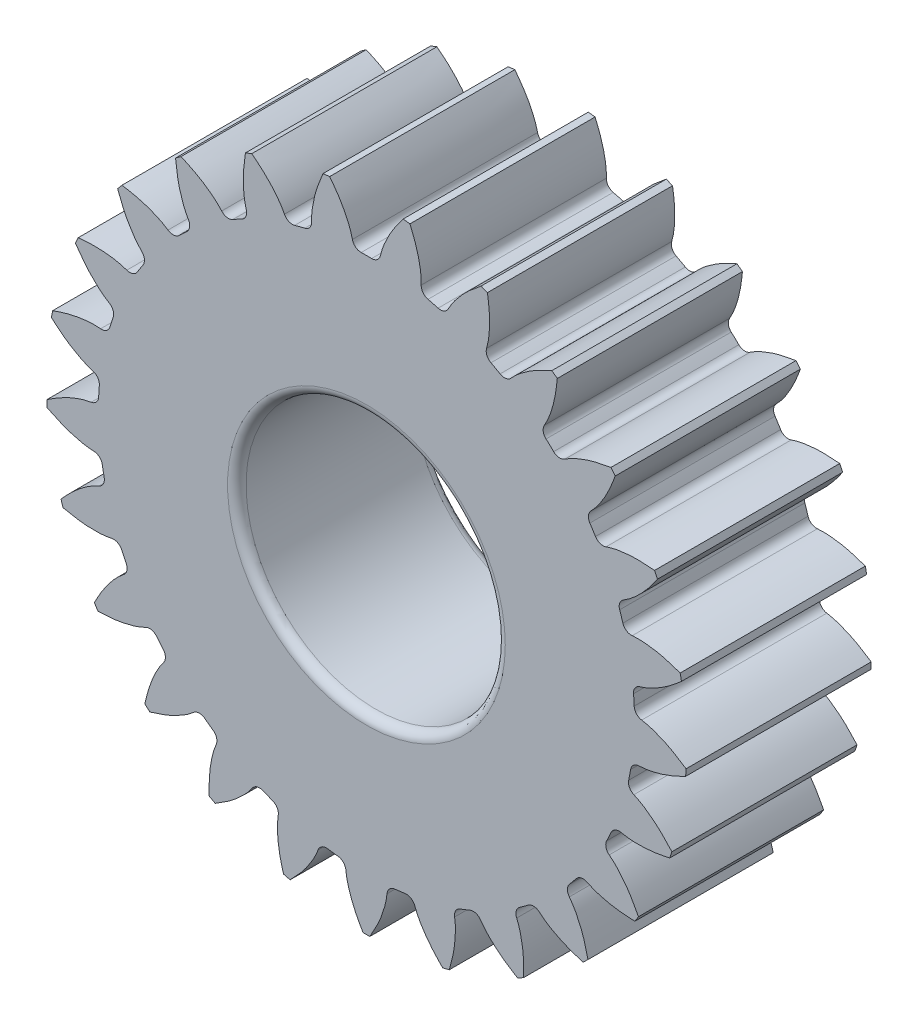
SolidWorks part; units mm, degrees
ref_plane "前视基准面" through (0, 0, 0) normal (0, 0, 1) x (1, 0, 0)
ref_plane "上视基准面" through (0, 0, 0) normal (0, 1, 0) x (1, 0, 0)
ref_plane "右视基准面" through (0, 0, 0) normal (1, 0, 0) x (0, 0, -1)
ref_axis "基准轴1" through (0, 0, -88.99) along (0, 0, 1)
sketch "草图1" plane through (0, 0, 0) normal (0, 0, 1) x (1, 0, 0)
  circle A0 centre (0, 0) radius 34.575
extrude "凸台-拉伸1" add sketch "草图1" along normal blind 20
sketch "草图2" plane through (0, 0, 0) normal (0, 0, -1) x (-1, 0, 0)
  arc A0 (0.5647, 28.9445) -> (-0.5647, 28.9445) centre (0, 0) ccw
  circle A1 centre (0, 0) radius 34.575
  arc A2 (3.9686, 34.3465) -> (-3.9686, 34.3465) centre (0, 0) ccw
  arc A3 (0.5647, 28.9445) -> (1.5123, 29.6963) centre (0.5832, 29.8943) ccw
  arc A4 (-0.5647, 28.9445) -> (-1.5123, 29.6963) centre (-0.5832, 29.8943) cw
  spline S0 degree 3 poles (1.5123, 29.6963) (1.5303, 29.7807) (1.6151, 30.119) (1.837, 30.8013) (2.2888, 31.8086) (2.9901, 33.0443) (3.6214, 33.8844) (3.9686, 34.3465) knots 0.129473 0.129473 0.129473 0.129473 0.17198 0.301359 0.482488 0.715369 1 1 1 1
  spline S1 degree 3 poles (-1.5123, 29.6963) (-1.5303, 29.7807) (-1.6151, 30.119) (-1.837, 30.8013) (-2.2888, 31.8086) (-2.9901, 33.0443) (-3.6214, 33.8844) (-3.9686, 34.3465) knots 0.129473 0.129473 0.129473 0.129473 0.17198 0.301359 0.482488 0.715369 1 1 1 1
  point P0 (1.4562, 29.3293)
  point P1 (1.4748, 29.4857)
  point P2 (1.5736, 29.9476)
  point P3 (1.8154, 30.697)
  point P4 (2.2594, 31.706)
  point P5 (2.9608, 32.9376)
  point P6 (3.9686, 34.3465)
  point P7 (-0.0283, 28.95)
  dimension "D2" = 0.95
  dimension "D3" = 0.95
  dimension "D1" = 0
extrude "切除-拉伸1" cut sketch "草图2" against normal blind 20
pattern_circular "阵列(圆周)1" count 25 over 360 about axis through (0, 0, -88.99) along (0, 0, 1) of "切除-拉伸1"
sketch "草图3" plane through (0, 0, 20) normal (0, 0, 1) x (1, 0, 0)
  circle A0 centre (0, 0) radius 14
extrude "切除-拉伸2" cut sketch "草图3" against normal through all
fillet "圆角1" radius 1 2 edges at (14, 0, 0) (14, 0, 20)
ref_plane "BaseFace1" through (0, 0, 0) normal (0, 0, -1) x (-1, 0, 0)
ref_plane "BaseFace2" through (0, 0, 20) normal (0, 0, 1) x (1, 0, 0)
